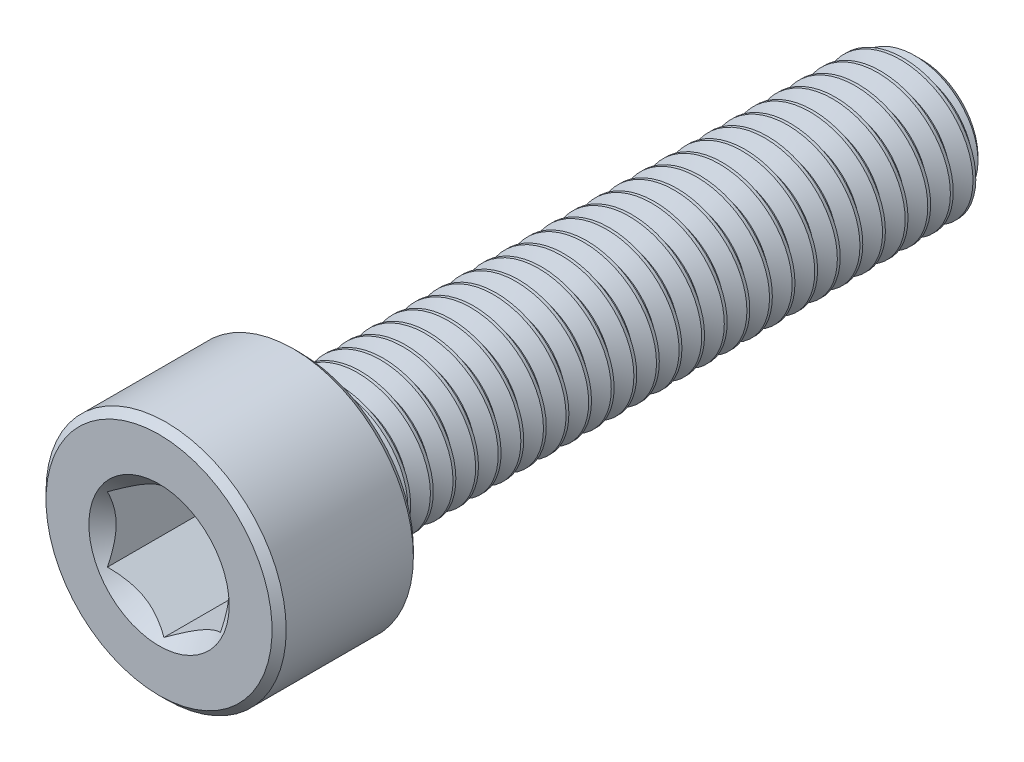
SolidWorks part; units mm, degrees
ref_plane "Front Plane" through (0, 0, 0) normal (0, 0, 1) x (1, 0, 0)
ref_plane "Top Plane" through (0, 0, 0) normal (0, 1, 0) x (1, 0, 0)
ref_plane "Right Plane" through (0, 0, 0) normal (1, 0, 0) x (0, 0, -1)
sketch "Sketch1" plane through (0, 0, 0) normal (1, 0, 0) x (0, 0, -1)
  line L0 (-13.5, 0) -> (13.5, 0) construction
  line L1 (13.5, 0) -> (13.5, 1.9804) construction
  line L2 (13.5, 1.9804) -> (12.9804, 2.5) construction
  line L3 (12.9804, 2.5) -> (12.9, 2.5) construction
  line L4 (12.9, 2.5) -> (-8.5, 2.5) construction
  line L5 (-8.5, 2.5) -> (-8.5, 4.25) construction
  line L6 (-8.5, 4.25) -> (-13.5, 4.25) construction
  line L7 (-13.5, 4.25) -> (-13.5, 0) construction
  line L8 (13.5, 1.9804) -> (13.5, 2.5) construction
  line L9 (13.45, 2.5866) -> (13.85, 1.8938) construction
  line L10 (13.85, 1.8938) -> (14.25, 2.5866) construction
  line L11 (14.25, 2.5866) -> (13.45, 2.5866) construction
  line L12 (13.85, 2.5866) -> (13.85, 2.5) construction
  line L13 (13.85, 1.8938) -> (13.85, 1.9804) construction
  line L14 (13.8, 1.9804) -> (13.9, 1.9804) construction
  line L15 (13.5, 2.5) -> (14.2, 2.5) construction
  line L16 (13.475, 2.5433) -> (14.225, 2.5433) construction
  line L17 (13.5, 0) -> (13.5, -2.5) construction
  line L18 (-8.75, 4.25) -> (-8.5, 4) construction
  line L19 (-13.25, 4.25) -> (-13.5, 4) construction
  line L20 (-8.5, 2.5) -> (-8.5, 0) construction
  line L21 (-8.5, 1.25) -> (-1.1667, 1.25) construction
  line L22 (-1.1667, 1.25) -> (6.1667, 1.25) construction
  line L23 (6.1667, 1.25) -> (13.5, 1.25) construction
  line L24 (-1.1667, 1.25) -> (-1.1667, 2.5) construction
  line L25 (-1.1667, 2.5) -> (-1.1667, 4.25) construction
  line L26 (6.1667, 1.25) -> (6.1667, 4.25) construction
  point P0 (-13.5, 2)
  point P3 (11.5, 2.5)
  point P4 (0, 0)
  point P18 (6.1667, 2.5)
  point P22 (13.85, 1.9804)
  point P24 (12.9, 2.5)
  point P25 (13.85, 2.5)
  point P28 (13.85, 2.5433)
  point P29 (11.5, -2.5)
  point P30 (-1.1667, 2.5)
  point P31 (-11, 4.25)
  point P37 (-9.375, 4.25)
  point P38 (-13.125, 4.25)
  point P45 (-1.1667, 1.25)
  point P46 (6.1667, 1.25)
  dimension "D2" = 0.1
  dimension "D7" = 0.25
  dimension "D8" = 0.25
  dimension "D9" = 0.25
  dimension "D10" = 0.125
  dimension "D11" = 0.625
  dimension "Drive Size" = 4
  dimension "Head Diameter" = 8.5
  dimension "Head Height" = 5
  dimension "Thread Pitch" = 0.8
  dimension "Thread Dia" = 5
  dimension "Length" = 22
  dimension "D12" = 0.6
  dimension "D4" = 2
  dimension "D3" = 45
sketch "Sketch2" plane through (0, 0, 0) normal (1, 0, 0) x (0, 0, -1)
  line L0 (-13.5, 0) -> (-13.5, 4)
  line L1 (-13.25, 4.25) -> (-8.75, 4.25)
  line L2 (-8.5, 4) -> (-8.5, 2.75)
  line L4 (12.9804, 2.5) -> (13.5, 1.9804)
  line L5 (13.5, 1.9804) -> (13.5, 0)
  line L6 (-8.5, 4.25) -> (-13.5, 4.25) construction
  line L7 (13.5, 0) -> (-13.5, 0)
  line L8 (-13.25, 4.25) -> (-13.5, 4) construction
  line L10 (-13.25, 4.25) -> (-13.5, 4)
  line L14 (-8.75, 4.25) -> (-8.5, 4) construction
  line L16 (-8.75, 4.25) -> (-8.5, 4)
  line L17 (-8.5, 2.5) -> (-8.5, 4.25) construction
  line L19 (-8.25, 2.5) -> (12.9804, 2.5)
  line L20 (12.9, 2.5) -> (-8.5, 2.5) construction
  arc A1 (-8.5, 2.75) -> (-8.25, 2.5) centre (-8.25, 2.75) ccw
  dimension "D3" = 0.25
revolve "Revolve1" add sketch "Sketch2" angle 360 about L7
sketch "Sketch3" plane through (0, 0, 13.5) normal (0, 0, 1) x (1, 0, 0)
  line L1 (2, -1.1547) -> (2, 1.1547)
  line L2 (2, 1.1547) -> (0, 2.3094)
  line L3 (0, 2.3094) -> (-2, 1.1547)
  line L4 (-2, 1.1547) -> (-2, -1.1547)
  line L5 (-2, -1.1547) -> (0, -2.3094)
  line L6 (0, -2.3094) -> (2, -1.1547)
  circle A0 centre (0, 0) radius 2 construction
  circle A1 centre (0, 0) radius 4.25 construction
  circle A2 centre (0, 0) radius 4.25 construction
  circle A3 centre (0, 0) radius 2.3094 construction
  point P13 (0, 0)
  dimension "D1" = 4.6188
extrude "Cut-Extrude1" cut sketch "Sketch3" against normal offset from surface (4 mm away) 1 up to face at (0, 4, 8.5)
sketch "Sketch4" plane through (0, 0, 13.5) normal (0, 0, 1) x (1, 0, 0)
  circle A0 centre (0, 0) radius 2.4826
  dimension "D1" = 4.9652
extrude "Cut-Extrude2" cut sketch "Sketch4" against normal up to vertex (2.5 mm away) draft 45 up to point (0, 4.25, 11)
sketch "Sketch11" plane through (0, 0, 0) normal (1, 0, 0) x (0, 0, -1)
  line L0 (-13.5, 0) -> (13.5, 0) construction
  line L1 (-13.5, 0) -> (13.5, 0) construction
  line L2 (-4.375, 0) -> (-4.375, 2.5) construction
  line L3 (12.9, 2.5) -> (-8.5, 2.5) construction
  line L4 (9.375, 0) -> (9.375, 2.5) construction
  line L6 (13.5, 1.9804) -> (13.5, 2.5) construction
  point P2 (-4.375, 0)
  point P3 (9.375, 0)
  dimension "D1" = 4.125
  dimension "D2" = 4.125
sketch "Sketch6" plane through (0, 0, -13.5) normal (0, 0, -1) x (-1, 0, 0)
  circle A0 centre (0, 0) radius 2.5
curve "Helix/Spiral1" pitch 0.8 height 22.8 turns 28.5
sketch "Sketch10" plane through (0, 0, 0) normal (1, 0, 0) x (0, 0, -1)
  line L0 (-8.25, -4.25) -> (-8.25, 4.25)
  line L5 (-13.5, 0) -> (13.5, 0) construction
  line L6 (-8.25, 2.5) -> (-8.25, -2.5) construction
  point P3 (-8.25, 0)
split "Split1" trim tools "Sketch10" bodies to split 106 resulting bodies 114 115
sketch "Sketch7" plane through (0, 0, 0) normal (1, 0, 0) x (0, 0, -1)
  line L0 (13.475, 2.5433) -> (14.225, 2.5433)
  line L1 (14.225, 2.5433) -> (13.9, 1.9804)
  line L2 (13.9, 1.9804) -> (13.8, 1.9804)
  line L3 (13.8, 1.9804) -> (13.475, 2.5433)
sweep "Cut-Sweep1" cut profiles "Sketch7" path "Helix/Spiral1" align with end faces yes
sketch "Sketch8" plane through (0, 0, 0) normal (1, 0, 0) x (0, 0, -1)
  line L0 (-8.5, 0) -> (-8.5, 2.5)
  line L1 (-8.25, -2.5) -> (-8.25, 2.5) construction
  line L2 (-8.5, 2.5) -> (-8.25, 2.5)
  line L4 (-8.25, 2.5) -> (-6.8066, 0)
  line L5 (-6.8066, 0) -> (-8.5, 0)
  line L6 (12.9, 2.5) -> (-8.5, 2.5) construction
  line L7 (-13.5, 0) -> (13.5, 0) construction
  dimension "D1" = 60
revolve "Revolve2" add sketch "Sketch8" angle 360 about L5
equation "\"D2@Sketch1\" = \"Thread Pitch@Sketch1\" / 8"
equation "\"D4@Helix/Spiral1\" = \"Thread Pitch@Sketch1\""
equation "\"D7@Sketch1\" = \"Head Height@Sketch1\" * .05"
equation "\"D8@Sketch1\"=\"D7@Sketch1\""
equation "\"D9@Sketch1\"=\"D7@Sketch1\""
equation "\"D10@Sketch1\"=\"D7@Sketch1\"/2"
equation "\"D11@Sketch1\"=\"D10@Sketch1\"*5"
equation "\"D4@Sketch1\"=\"Thread Pitch@Sketch1\"*2.5"
equation "\"D12@Sketch1\"=\"Thread Pitch@Sketch1\"*.75"
equation "\"D3@Helix/Spiral1\"=\"Length@Sketch1\"+\"Thread Pitch@Sketch1\""
equation "\"D3@Sketch2\"=\"Thread Dia@Sketch1\"*0.05"
equation "\"D1@Sketch11\"=\"Length@Sketch1\"*0.1875"
equation "\"D2@Sketch11\"=\"D1@Sketch11\""
equation "\"D1@Sketch4\"=\"D1@Sketch3\"*1.075"
